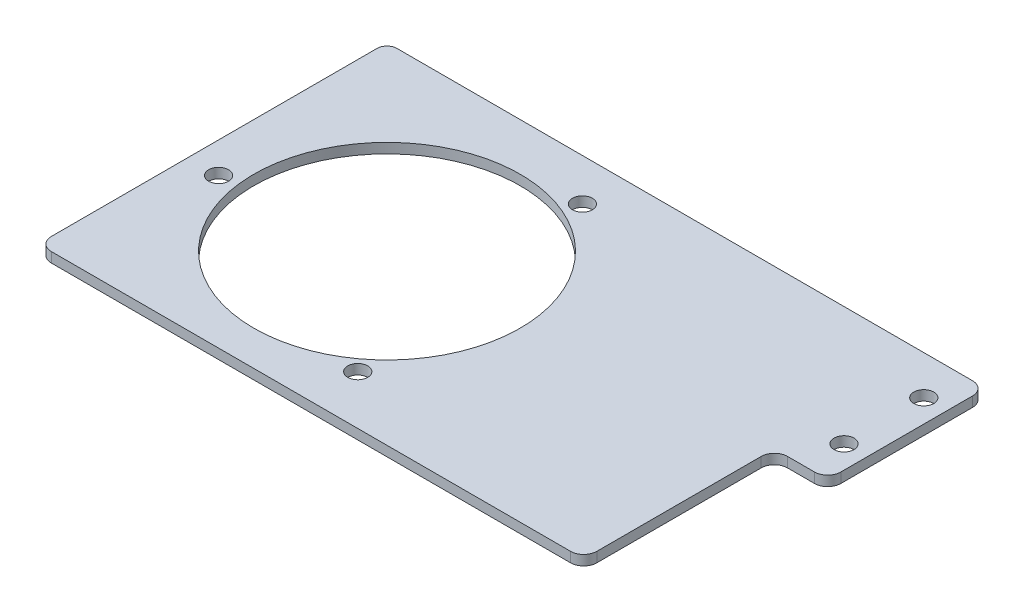
SolidWorks part; units mm, degrees
ref_plane "Front Plane" through (0, 0, 0) normal (0, 0, 1) x (1, 0, 0)
ref_plane "Top Plane" through (0, 0, 0) normal (0, 1, 0) x (1, 0, 0)
ref_plane "Right Plane" through (0, 0, 0) normal (1, 0, 0) x (0, 0, -1)
sketch "Sketch5" plane through (0, 0, 0) normal (0, 1, 0) x (1, 0, 0)
  line L0 (-108.5113, 114.8574) -> (257.5911, 114.8574)
  line L1 (265.9438, 106.5046) -> (265.9438, 22.6846)
  line L2 (257.5911, 14.3319) -> (240.397, 14.3319)
  line L3 (232.0442, 5.9791) -> (232.0442, -98.5839)
  line L4 (223.6915, -106.9367) -> (-106.5085, -106.9367)
  line L5 (-114.8613, -98.5839) -> (-114.8613, 108.5074)
  line L6 (265.9438, 64.5946) -> (253.9936, 64.5946) construction
  arc A0 (-108.5113, 114.8574) -> (-114.8613, 108.5074) centre (-108.5113, 108.5074) ccw
  arc A1 (-106.5085, -106.9367) -> (-114.8613, -98.5839) centre (-106.5085, -98.5839) cw
  arc A2 (232.0442, -98.5839) -> (223.6915, -106.9367) centre (223.6915, -98.5839) cw
  arc A3 (240.397, 14.3319) -> (232.0442, 5.9791) centre (240.397, 5.9791) ccw
  arc A4 (265.9438, 22.6846) -> (257.5911, 14.3319) centre (257.5911, 22.6846) cw
  arc A5 (257.5911, 114.8574) -> (265.9438, 106.5046) centre (257.5911, 106.5046) cw
  circle A6 centre (0, 0) radius 84.7725
  circle A7 centre (251.46, 89.9682) radius 6.35
  circle A8 centre (251.46, 39.2211) radius 6.35
  circle A9 centre (-95.2384, -11.8444) radius 6.35
  circle A12 centre (57.0353, -75.6468) radius 6.35
  circle A14 centre (36.1529, 88.1273) radius 6.35
  point P37 (0, 0)
  dimension "D1" = 6.35
  dimension "D2" = 169.545
  dimension "D3" = 207.0913
  dimension "D4" = 366.1024
  dimension "D5" = 83.82
  dimension "D6" = 330.2
  dimension "D7" = 104.563
extrude "Boss-Extrude1" add sketch "Sketch5" against normal blind 6.35 contours A5 L1 A4 L2 A3 L3 A2 L4 A1 L5 A0 L0 | A6 | A7 | A8 | A9 | A14 | A12
